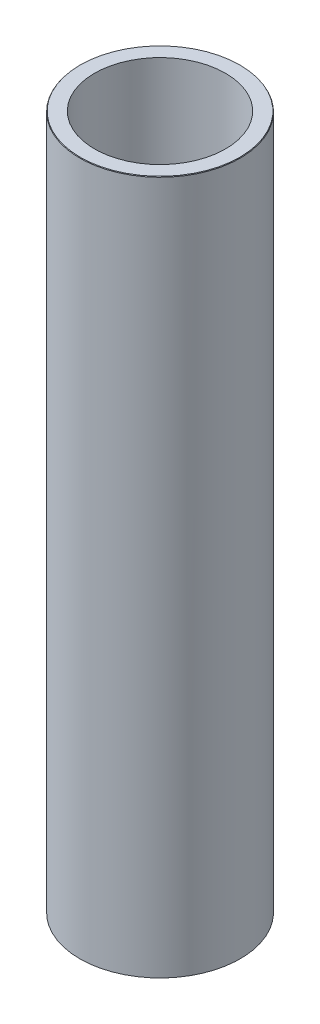
SolidWorks part; units mm, degrees
ref_plane "Front Plane" through (0, 0, 0) normal (0, 0, 1) x (1, 0, 0)
ref_plane "Top Plane" through (0, 0, 0) normal (0, 1, 0) x (1, 0, 0)
ref_plane "Right Plane" through (0, 0, 0) normal (1, 0, 0) x (0, 0, -1)
sketch "Sketch1" plane through (0, 0, 0) normal (0, 1, 0) x (1, 0, 0)
  circle A0 centre (0, 0) radius 50
  dimension "SHAFT_OD" = 100
extrude "Boss-Extrude1" add sketch "Sketch1" along normal blind 432.6416
sketch "Sketch2" plane through (0, 0, 0) normal (0, 1, 0) x (1, 0, 0)
  circle A0 centre (0, 0) radius 40.8459
  dimension "BORE_D" = 81.6918
extrude "Cut-Extrude1" cut sketch "Sketch2" along normal through all
chamfer "Chamfer1" distance 0.3864 angle 32.436 2 edges at (0, 432.6416, 50) (0, 0, 50) first distance on face at (0, 432.6416, 50) first distance on face at (0, 0, 40.8459)
